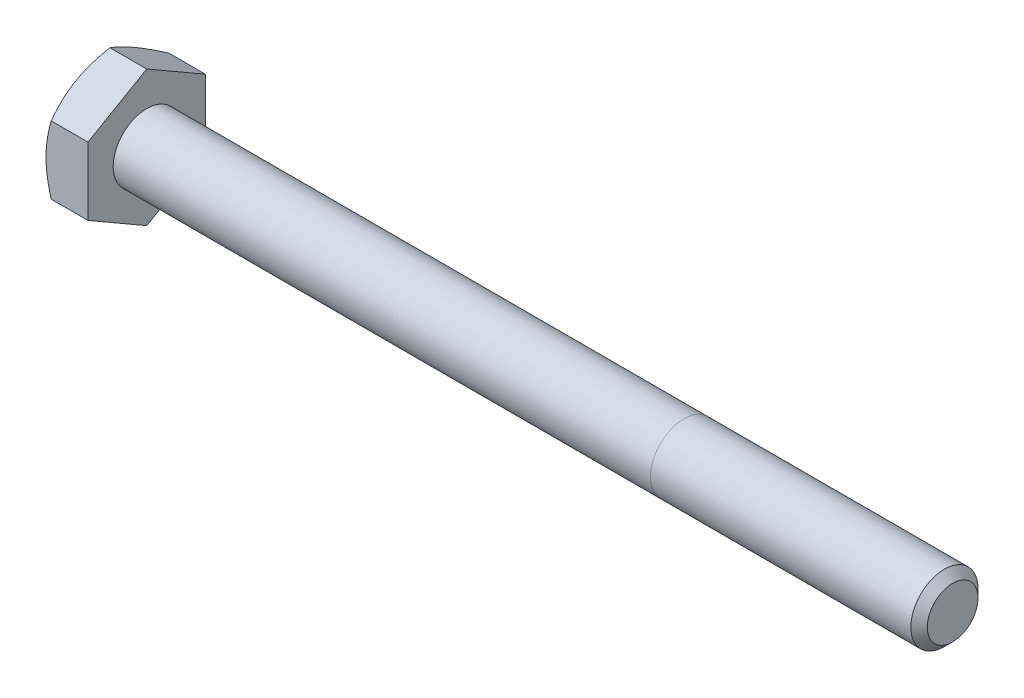
SolidWorks part; units mm, degrees
material "Alloy Steel"
ref_plane "Front Plane" through (0, 0, 0) normal (0, 0, 1) x (1, 0, 0)
ref_plane "Top Plane" through (0, 0, 0) normal (0, 1, 0) x (1, 0, 0)
ref_plane "Right Plane" through (0, 0, 0) normal (1, 0, 0) x (0, 0, -1)
sketch "Sketch1" plane through (0, 0, 0) normal (0, 0, 1) x (1, 0, 0)
  line L0 (-40.0844, 0) -> (40.0844, 0) construction
  line L1 (40.0844, 3.175) -> (40.0844, -3.175) construction
  line L2 (-36.1156, 5.5562) -> (-36.1156, -5.5562) construction
  line L3 (-40.0844, 5.5562) -> (-40.0844, -5.5562) construction
  point P9 (-36.1156, 0)
  point P10 (35.6394, -3.175)
  point P11 (14.6844, 0)
  dimension "D1" = 4.445
  dimension "Screw Dia" = 6.35
  dimension "Hex" = 11.1125
  dimension "Head Ht" = 3.9688
  dimension "Screw Lenght" = 76.2
  dimension "D2" = 25.4
ref_plane "Plane2" through (40.0844, 0, 0) normal (1, 0, 0) x (0, 0, -1)
sketch "Sketch5" plane through (40.0844, 0, 0) normal (1, 0, 0) x (0, 0, -1)
  circle A0 centre (0, 0) radius 3.175
extrude "Boss-Extrude3" add sketch "Sketch5" against normal up to vertex (76.2 mm away) up to point (-36.1156, 0, 0)
sketch "Sketch9" plane through (40.0844, 0, 0) normal (1, 0, 0) x (0, 0, -1)
  circle A1 centre (0, 0) radius 3.175
  circle A2 centre (0, 0) radius 3.175
  dimension "D1" = 0
curve "Helix/Spiral1" pitch 1.27 height 77.47 turns 61 parameters "Pitch"=1.27
chamfer "Chamfer1" distance 0.7772 angle 45 1 edges at (40.0844, 0, -3.175)
sketch "Sketch10" plane through (0, 0, 0) normal (0, 0, 1) x (1, 0, 0)
  line L0 (40.0844, 3.175) -> (40.5606, 2.3501)
  line L1 (40.5606, 2.3501) -> (40.7194, 2.3501)
  line L2 (40.7194, 2.3501) -> (41.1956, 3.175)
  line L3 (40.0844, 3.175) -> (41.1956, 3.175)
  line L4 (40.64, 3.175) -> (40.64, 2.3501) construction
  line L5 (40.3225, 2.7626) -> (40.9575, 2.7626) construction
  dimension "D1" = 60
  dimension "D2" = 0.1588
  dimension "D3" = 0.635
sketch "Sketch6" plane through (-36.1156, 0, 0) normal (-1, 0, 0) x (0, 0, 1)
  line L0 (0, 5.5562) -> (0, -5.5562) construction
  line L1 (5.5563, 3.2079) -> (0, 6.4158)
  line L2 (0, 6.4158) -> (-5.5562, 3.2079)
  line L3 (-5.5562, 3.2079) -> (-5.5562, -3.2079)
  line L4 (-5.5562, -3.2079) -> (0, -6.4158)
  line L5 (0, -6.4158) -> (5.5563, -3.2079)
  line L6 (5.5563, -3.2079) -> (5.5563, 3.2079)
  circle A0 centre (0, 0) radius 5.5563 construction
extrude "Boss-Extrude4" add sketch "Sketch6" along normal up to vertex (3.9688 mm away) up to point (-40.0844, -5.5562, 0)
sketch "Sketch7" plane through (-40.0844, 0, 0) normal (-1, 0, 0) x (0, 0, 1)
  circle A0 centre (0, 0) radius 5.5563 construction
  circle A1 centre (0, 0) radius 5.5563
sketch "Sketch8" plane through (-40.0844, 0, 0) normal (-1, 0, 0) x (0, 0, 1)
  circle A0 centre (0, 0) radius 5.5563 construction
  circle A1 centre (0, 0) radius 5.5563
extrude "Cut-Extrude3" cut sketch "Sketch8" against normal through all draft 60 flip side to cut
sketch "Sketch12" plane through (-40.0844, 0, 0) normal (-1, 0, 0) x (0, 0, 1)
  line L0 (0, 4.2783) -> (0, 2.3892) construction
  line L1 (0.1667, 4.2783) -> (0.1667, 2.3892)
  line L2 (-0.1667, 4.2783) -> (-0.1667, 2.3892)
  line L3 (0, 3.175) -> (0, -3.175) construction
  arc A0 (0.1667, 4.2783) -> (-0.1667, 4.2783) centre (0, 4.2783) ccw
  arc A1 (-0.1667, 2.3892) -> (0.1667, 2.3892) centre (0, 2.3892) ccw
  circle A3 centre (0, 0) radius 2.2225 construction
  circle A4 centre (0, 0) radius 4.445 construction
  point P2 (0, 3.3337)
  dimension "D1" = 4.445
  dimension "D3" = 8.89
  dimension "D2" = 0.3334
extrude "Cut-Extrude4" cut sketch "Sketch12" against normal blind 0.254
pattern_circular "CirPattern1" count 3 over 360 about axis through (-36.1156, 0, 0) along (1, 0, 0) of "Cut-Extrude4"
sketch "Sketch13" plane through (0, 0, 0) normal (0, 0, 1) x (1, 0, 0)
  line L0 (14.6844, 3.175) -> (14.6844, -3.175)
  line L2 (-36.1156, -3.175) -> (39.3071, -3.175) construction
  point P4 (14.6844, 0)
split line "Split Line1"
equation "\"D2@Sketch10\" = \"Pitch@Helix/Spiral1\"*.125"
equation "\"D3@Sketch10\" = \"Pitch@Helix/Spiral1\"*.5"
equation "\"D1@Chamfer1\" = \"Pitch@Helix/Spiral1\"*.612"
equation "\"D1@Sketch12\" = \"Hex@Sketch1\"*.4"
equation "\"D3@Sketch12\" = \"Hex@Sketch1\"*.8"
equation "\"D2@Sketch12\" = \"Hex@Sketch1\"*.03"
equation "\"D1@Sketch1\" = \"Pitch@Helix/Spiral1\"*3.5"
equation "\"D3@Helix/Spiral1\" = \"Screw Lenght@Sketch1\"+\"Pitch@Helix/Spiral1\""
